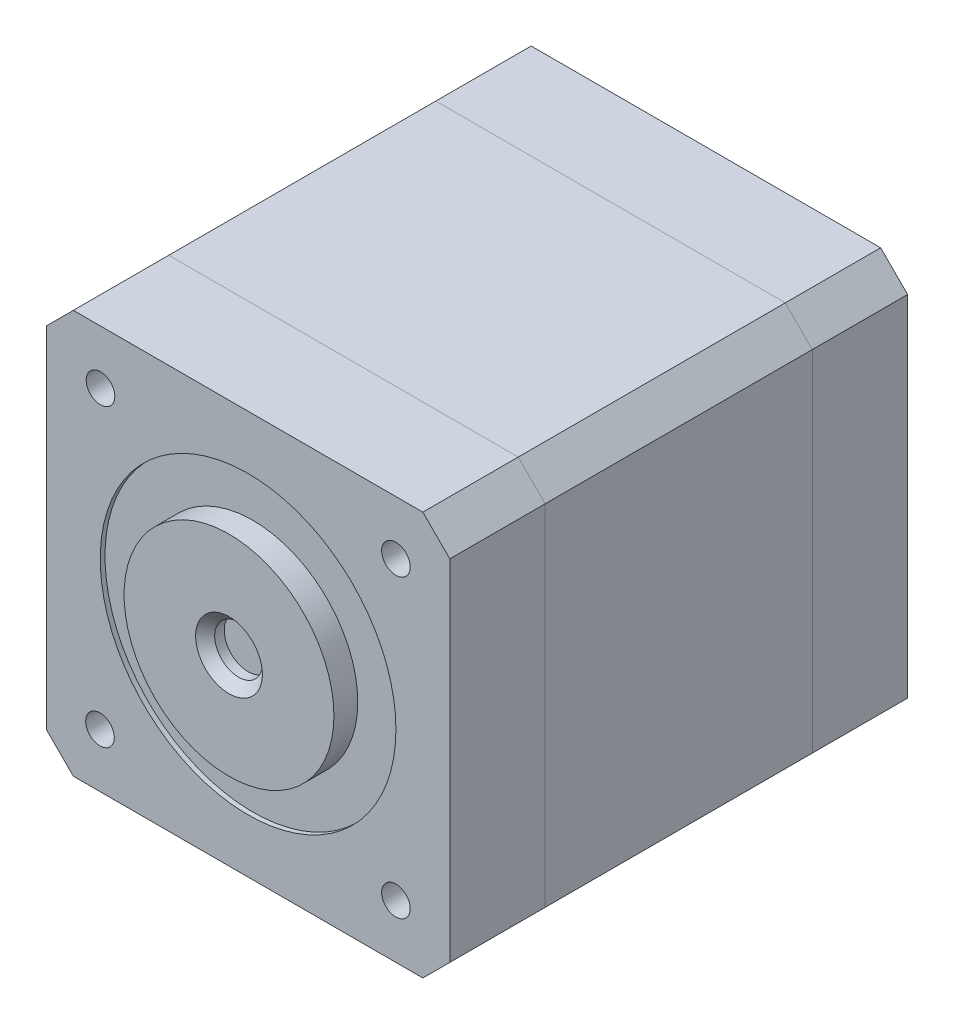
SolidWorks part; units mm, degrees
ref_plane "前视基准面" through (0, 0, 0) normal (0, 0, 1) x (1, 0, 0)
ref_plane "上视基准面" through (0, 0, 0) normal (0, 1, 0) x (1, 0, 0)
ref_plane "右视基准面" through (0, 0, 0) normal (1, 0, 0) x (0, 0, -1)
sketch "草图1" plane through (0, 0, 0) normal (0, 0, 1) x (1, 0, 0)
  line L0 (0, -21.15) -> (0, 21.15) construction
  line L1 (18.3216, 21.15) -> (-18.3216, 21.15)
  line L2 (-18.3216, 21.15) -> (-21.15, 18.3216)
  line L3 (-21.15, 18.3216) -> (-21.15, -18.3216)
  line L4 (-21.15, -18.3216) -> (-18.3216, -21.15)
  line L5 (-18.3216, -21.15) -> (18.3216, -21.15)
  line L6 (21.15, -18.3216) -> (18.3216, -21.15)
  line L7 (18.3216, 21.15) -> (21.15, 18.3216)
  line L8 (21.15, 18.3216) -> (21.15, -18.3216)
  line L9 (-19.7358, 19.7358) -> (0, 0) construction
  line L10 (-15.5, 15.5) -> (15.5, 15.5) construction
  circle A4 centre (0, 0) radius 15.5
  circle A6 centre (0, 0) radius 11
  circle A8 centre (0, 0) radius 2.5
  dimension "D8" = 5
  dimension "D9" = 22
  dimension "D1" = 135
  dimension "D2" = 42.3
  dimension "D3" = 42.3
  dimension "D4" = 4
  dimension "D6" = 31
extrude "凸台-拉伸1" add sketch "草图1" against normal blind 10 contours L8 L7 L1 L2 L3 L4 L5 L6 A4 | A4 | A6 | A6 | A8 | A8 region at (19.3128, 19.3128, 0) region at (-15.0616, 0, 0) region at (-10.6889, 0, 0) region at (0, 0, 0)
sketch "草图2" plane through (0, 0, -10) normal (0, 0, -1) x (-1, 0, 0)
  line L8 (-21.15, 18.3216) -> (-21.15, -18.3216)
  line L9 (-21.15, -18.3216) -> (-18.3216, -21.15)
  line L10 (-18.3216, -21.15) -> (18.3216, -21.15)
  line L11 (18.3216, -21.15) -> (21.15, -18.3216)
  line L12 (21.15, -18.3216) -> (21.15, 18.3216)
  line L13 (21.15, 18.3216) -> (18.3216, 21.15)
  line L14 (18.3216, 21.15) -> (-18.3216, 21.15)
  line L15 (-18.3216, 21.15) -> (-21.15, 18.3216)
  line L16 (-21.15, 18.3216) -> (-21.15, -18.3216)
  line L17 (-21.15, -18.3216) -> (-18.3216, -21.15)
  line L18 (-18.3216, -21.15) -> (18.3216, -21.15)
  line L19 (18.3216, -21.15) -> (21.15, -18.3216)
  line L20 (21.15, -18.3216) -> (21.15, 18.3216)
  line L21 (21.15, 18.3216) -> (18.3216, 21.15)
  line L22 (18.3216, 21.15) -> (-18.3216, 21.15)
  line L23 (-18.3216, 21.15) -> (-21.15, 18.3216)
  dimension "D1" = 0
extrude "凸台-拉伸2" add sketch "草图2" along normal blind 28 separate body
sketch "草图3" plane through (0, 0, -38) normal (0, 0, -1) x (-1, 0, 0)
  line L8 (-18.3216, 21.15) -> (-21.15, 18.3216)
  line L9 (-21.15, 18.3216) -> (-21.15, -18.3216)
  line L10 (-21.15, -18.3216) -> (-18.3216, -21.15)
  line L11 (-18.3216, -21.15) -> (18.3216, -21.15)
  line L12 (18.3216, -21.15) -> (21.15, -18.3216)
  line L13 (21.15, -18.3216) -> (21.15, 18.3216)
  line L14 (21.15, 18.3216) -> (18.3216, 21.15)
  line L15 (18.3216, 21.15) -> (-18.3216, 21.15)
  line L16 (-18.3216, 21.15) -> (-21.15, 18.3216)
  line L17 (-21.15, 18.3216) -> (-21.15, -18.3216)
  line L18 (-21.15, -18.3216) -> (-18.3216, -21.15)
  line L19 (-18.3216, -21.15) -> (18.3216, -21.15)
  line L20 (18.3216, -21.15) -> (21.15, -18.3216)
  line L21 (21.15, -18.3216) -> (21.15, 18.3216)
  line L22 (21.15, 18.3216) -> (18.3216, 21.15)
  line L23 (18.3216, 21.15) -> (-18.3216, 21.15)
  dimension "D1" = 0
extrude "凸台-拉伸3" add sketch "草图3" along normal blind 10 separate body
extrude "切除-拉伸1" cut sketch "草图1<3>" against normal blind 0.5 contours A4 region at (-15.0616, 0, 0)
sketch "草图1<3>" plane through (0, 0, 0) normal (0, 0, 1) x (1, 0, 0) same geometry as "草图1"
extrude "凸台-拉伸4" add sketch "草图1<4>" along normal blind 2 contours A6 region at (-10.6889, 0, 0)
sketch "草图1<4>" plane through (0, 0, 0) normal (0, 0, 1) x (1, 0, 0) same geometry as "草图1"
chamfer "倒角1" distance 1 1 edges at (2.5, 0, 2)
sketch "草图5" plane through (0, 0, 0) normal (0, 0, 1) x (1, 0, 0)
  line L0 (0, 0) -> (-22.9145, 22.9537) construction
  line L1 (0, 0) -> (26.811, 26.811) construction
  line L2 (0, 0) -> (28.5218, -28.5706) construction
  line L3 (0, 0) -> (-28.6373, -28.5884) construction
  line L4 (-15.5, 27.9337) -> (-15.5, -34.8707) construction
  line L5 (32.3867, 15.5) -> (-43.7066, 15.5) construction
  line L6 (15.5, 27.9337) -> (15.5, -34.8707) construction
  line L7 (24.7503, -15.5) -> (-29.9309, -15.5) construction
  circle A0 centre (-15.4734, 15.5) radius 1.5
  circle A1 centre (15.5, 15.5) radius 1.5
  circle A2 centre (15.5, -15.5265) radius 1.5
  circle A3 centre (-15.5265, -15.5) radius 1.5
  circle A4 centre (0, 0) radius 15.5 construction
  circle A6 centre (0, 0) radius 15.5 construction
  dimension "D2" = 3
  dimension "D3" = 3
  dimension "D4" = 3
  dimension "D5" = 3
  dimension "D1" = 31
extrude "切除-拉伸3" cut sketch "草图5" against normal blind 3
